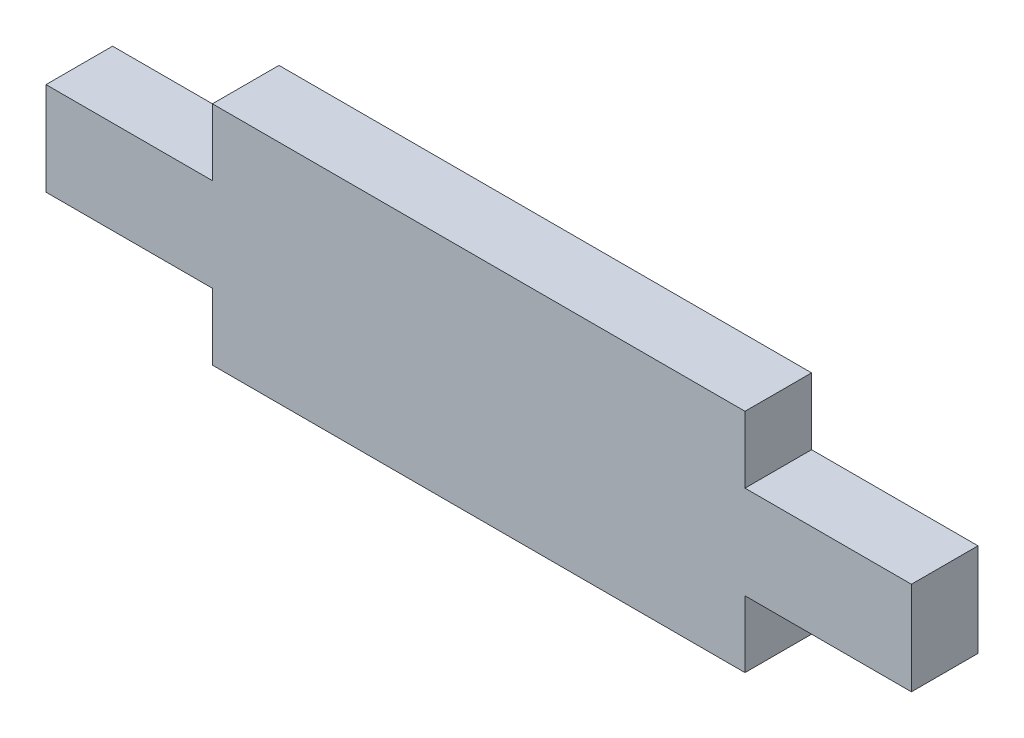
SolidWorks part; units mm, degrees
ref_plane "Front" through (0, 0, 0) normal (0, 0, 1) x (1, 0, 0)
ref_plane "Top" through (0, 0, 0) normal (0, 1, 0) x (1, 0, 0)
ref_plane "Right" through (0, 0, 0) normal (1, 0, 0) x (0, 0, -1)
sketch "Skizze1" plane through (0, 0, 0) normal (0, 0, 1) x (1, 0, 0)
  line L1 (0, 0) -> (65, 0)
  line L2 (0, 0) -> (0, -7)
  line L3 (0, -7) -> (65, -7)
  line L4 (65, 0) -> (65, -7)
  dimension "D1" = 7
  dimension "D2" = 65
extrude "Aufsatz-Linear austragen1" add sketch "Skizze1" along normal blind 5
sketch "Skizze2" plane through (0, 0, 0) normal (0, 1, 0) x (1, 0, 0)
  line L0 (32.5, 0) -> (32.5, -5) construction
  line L1 (65, 0) -> (0, 0) construction
  line L2 (65, -5) -> (0, -5) construction
  line L3 (52.5, 0) -> (12.5, 0)
  line L4 (12.5, 0) -> (12.5, -5)
  line L5 (12.5, -5) -> (52.5, -5)
  line L6 (52.5, 0) -> (52.5, -5)
  dimension "D1" = 40
extrude "Aufsatz-Linear austragen3" add sketch "Skizze2" along normal blind 5
ref_plane "Ebene1" through (0, -3.5, 0) normal (0, 1, 0) x (1, 0, 0)
mirror "Spiegeln1" about plane through (0, -3.5, 0) normal (0, 1, 0) of "Aufsatz-Linear austragen3"
